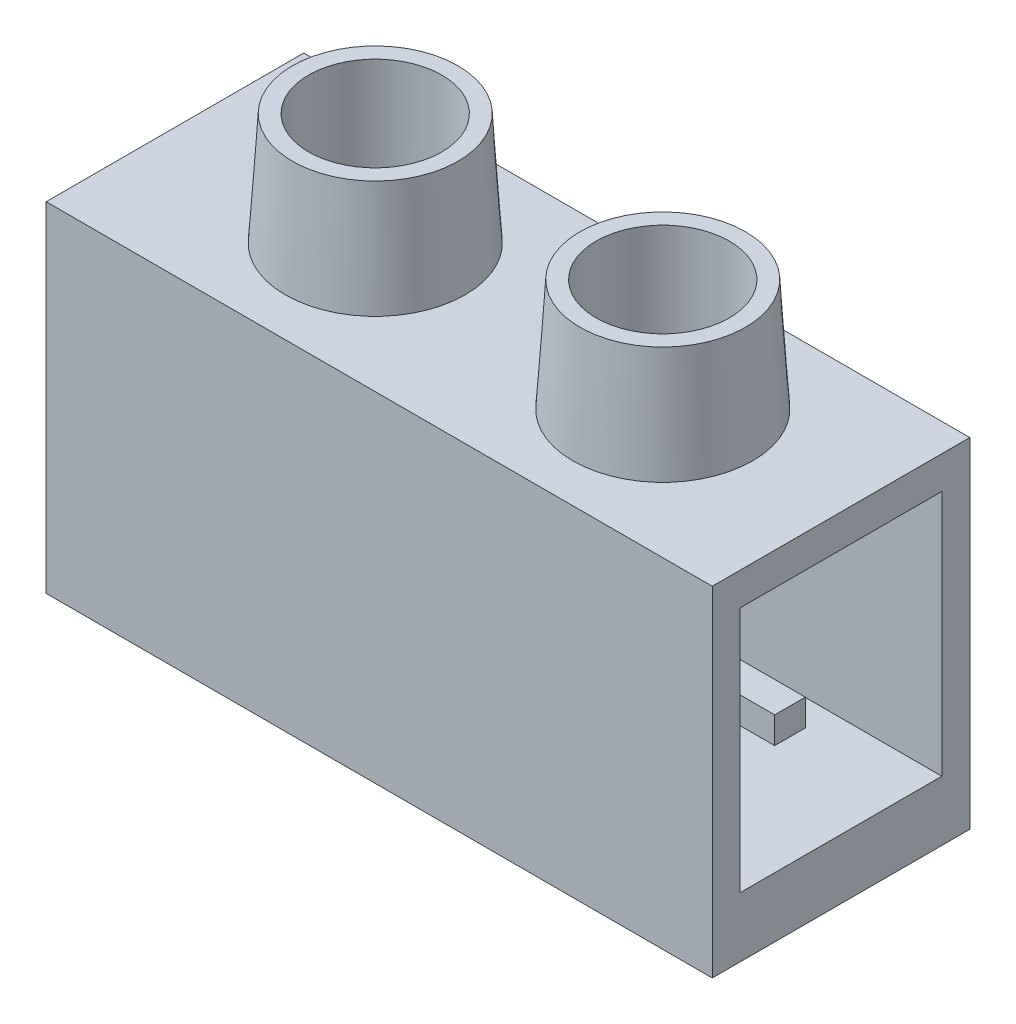
SolidWorks part; units mm, degrees
ref_plane "Front Plane" through (0, 0, 0) normal (0, 0, 1) x (1, 0, 0)
ref_plane "Top Plane" through (0, 0, 0) normal (0, 1, 0) x (1, 0, 0)
ref_plane "Right Plane" through (0, 0, 0) normal (1, 0, 0) x (0, 0, -1)
sketch "Sketch1" plane through (0, 0, 0) normal (0, 1, 0) x (1, 0, 0)
  line L0 (-3.25, 5.8) -> (-15, 5.8)
  line L1 (15, -5.8) -> (-15, -5.8)
  line L2 (15, -5.8) -> (15, 5.8)
  line L3 (15, 5.8) -> (3.25, 5.8)
  line L4 (-15, -5.8) -> (-15, 5.8)
  line L5 (15, -5.8) -> (-15, 5.8) construction
  line L6 (15, 5.8) -> (-15, -5.8) construction
  line L13 (-3.25, 5.8) -> (3.25, 5.8)
  point P0 (0, 0)
  dimension "D1" = 11.6
  dimension "D2" = 30
extrude "Boss-Extrude1" add sketch "Sketch1" along normal blind 15.28
sketch "Sketch2" plane through (0, 15.28, 0) normal (0, 1, 0) x (1, 0, 0)
  line L0 (-15, 5.8) -> (-15, -5.8) construction
  line L1 (15, -5.8) -> (15, 5.8) construction
  circle A0 centre (-5.98, 0) radius 4.05
  circle A1 centre (6.97, 0) radius 4.05
  dimension "D1" = 8.1
  dimension "D2" = 8.1
  dimension "D3" = 9.02
  dimension "D4" = 8.03
extrude "Boss-Extrude2" add sketch "Sketch2" along normal blind 9.72
chamfer "Chamfer1" distance 9.72 distance2 0.62 1 edges at (-5.98, 25, 4.05) first distance on face at (-5.98, 25, 4.05)
chamfer "Chamfer2" distance 9.72 distance2 0.62 1 edges at (6.97, 25, 4.05) first distance on face at (6.97, 25, 4.05)
sketch "Sketch4" plane through (15, 0, 0) normal (1, 0, 0) x (0, 0, -1)
  line L0 (-5.8, 0) -> (5.8, 0) construction
  line L1 (4.54, 2.7) -> (-4.54, 2.7)
  line L2 (4.54, 2.7) -> (4.54, 13.81)
  line L3 (4.54, 13.81) -> (-4.54, 13.81)
  line L4 (-4.54, 2.7) -> (-4.54, 13.81)
  line L5 (4.54, 2.7) -> (-4.54, 13.81) construction
  line L6 (4.54, 13.81) -> (-4.54, 2.7) construction
  line L7 (-5.8, 15.28) -> (-5.8, 0) construction
  line L8 (-5.8, 15.28) -> (5.8, 15.28) construction
  point P0 (0, 8.255)
  point P10 (0, 0)
  dimension "D1" = 2.7
  dimension "D2" = 1.26
  dimension "D3" = 1.47
extrude "Cut-Extrude1" cut sketch "Sketch4" against normal up to surface (30 mm away) up to face at (-15, 7.64, 0)
sketch "Sketch6" plane through (-15, 0, 0) normal (-1, 0, 0) x (0, 0, 1)
  line L0 (4.54, 13.81) -> (-4.54, 13.81) construction
  line L1 (-0.75, 10.81) -> (0.75, 10.81)
  line L2 (-0.75, 10.81) -> (-0.75, 13.81)
  line L3 (-0.75, 13.81) -> (0.75, 13.81)
  line L4 (0.75, 10.81) -> (0.75, 13.81)
  line L5 (-0.75, 10.81) -> (0.75, 13.81) construction
  line L6 (-0.75, 13.81) -> (0.75, 10.81) construction
  line L7 (-4.54, 2.7) -> (4.54, 2.7) construction
  line L8 (-4.54, 13.81) -> (-2.97, 13.81)
  line L9 (-4.54, 13.81) -> (-4.54, 10.81)
  line L10 (-4.54, 10.81) -> (-2.97, 10.81)
  line L11 (-2.97, 13.81) -> (-2.97, 10.81)
  line L12 (-3.35, 2.7) -> (-1.97, 2.7)
  line L13 (-3.35, 2.7) -> (-3.35, 3.9)
  line L14 (-3.35, 3.9) -> (-1.97, 3.9)
  line L15 (-1.97, 2.7) -> (-1.97, 3.9)
  line L16 (-4.54, 13.81) -> (-4.54, 2.7) construction
  line L17 (0, 2.7) -> (0, 13.81) construction
  line L18 (1.97, 2.7) -> (1.97, 3.9)
  line L19 (3.35, 3.9) -> (1.97, 3.9)
  line L20 (3.35, 2.7) -> (3.35, 3.9)
  line L21 (3.35, 2.7) -> (1.97, 2.7)
  line L22 (2.97, 13.81) -> (2.97, 10.81)
  line L23 (4.54, 10.81) -> (2.97, 10.81)
  line L24 (4.54, 13.81) -> (4.54, 10.81)
  line L25 (4.54, 13.81) -> (2.97, 13.81)
  point P0 (0, 12.31)
  dimension "D1" = 1.5
  dimension "D2" = 3
  dimension "D3" = 1.57
  dimension "D4" = 1.19
  dimension "D5" = 1.38
  dimension "D6" = 1.2
  dimension "D7" = 3
extrude "Boss-Extrude3" add sketch "Sketch6" against normal blind 25.0423
sketch "Sketch7" plane through (10.0423, 0, 0) normal (1, 0, 0) x (0, 0, -1)
  line L4 (-0.75, 13.81) -> (-0.75, 10.81)
  line L5 (-0.75, 10.81) -> (0.75, 10.81)
  line L6 (0.75, 10.81) -> (0.75, 13.81)
  line L7 (0.75, 13.81) -> (-0.75, 13.81)
  line L8 (-0.75, 13.81) -> (-0.75, 10.81)
  line L9 (-0.75, 10.81) -> (0.75, 10.81)
  line L10 (0.75, 10.81) -> (0.75, 13.81)
  line L11 (0.75, 13.81) -> (-0.75, 13.81)
  dimension "D1" = 0
extrude "Cut-Extrude2" cut sketch "Sketch7" against normal blind 19.72
sketch "Sketch8" plane through (0, 25, 0) normal (0, 1, 0) x (1, 0, 0)
  circle A0 centre (6.97, 0) radius 3
  circle A1 centre (-5.98, 0) radius 3
  dimension "D1" = 6
  dimension "D2" = 6
extrude "Cut-Extrude3" cut sketch "Sketch8" against normal up to surface (11.19 mm away) up to face at (-0.7655, 13.81, 0)
sketch "Sketch9" plane through (-15, 0, 0) normal (-1, 0, 0) x (0, 0, 1)
  line L0 (3.43, 25) -> (-3.43, 25) construction
  line L1 (-5.8, 20.33) -> (5.8, 20.33)
  line L2 (-5.8, 20.33) -> (-5.8, 25)
  line L3 (-5.8, 25) -> (5.8, 25)
  line L4 (5.8, 20.33) -> (5.8, 25)
  line L5 (-5.8, 0) -> (5.8, 0) construction
  dimension "D1" = 20.33
extrude "Cut-Extrude4" cut sketch "Sketch9" against normal blind 32
